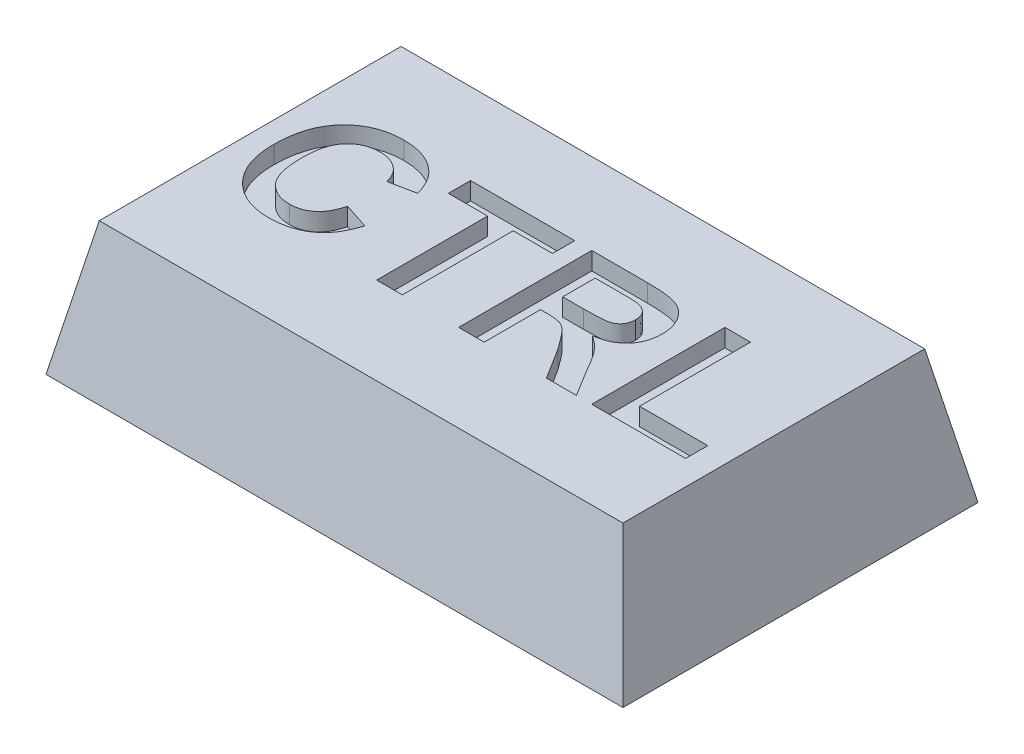
SolidWorks part; units mm, degrees
ref_plane "Front Plane" through (0, 0, 0) normal (0, 0, 1) x (1, 0, 0)
ref_plane "Top Plane" through (0, 0, 0) normal (0, 1, 0) x (1, 0, 0)
ref_plane "Right Plane" through (0, 0, 0) normal (1, 0, 0) x (0, 0, -1)
sketch "Sketch1" plane through (0, 0, 0) normal (0, 1, 0) x (1, 0, 0)
  line L1 (0, 0) -> (13, 0)
  line L2 (0, 0) -> (0, 8)
  line L3 (0, 8) -> (13, 8)
  line L4 (13, 0) -> (13, 8)
  dimension "D1" = 8
  dimension "D2" = 13
extrude "Boss-Extrude1" add sketch "Sketch1" along normal blind 3
sketch "Sketch2" plane through (0, 0, 0) normal (0, 0, 1) x (1, 0, 0)
  line L0 (0, 0) -> (0.6, 3)
  line L1 (0, 3) -> (13, 3) construction
  line L2 (0.6, 3) -> (0, 3)
  line L3 (0, 3) -> (0, 0)
  line L4 (13, 0) -> (12.4, 3)
  line L5 (12.4, 3) -> (13, 3)
  line L6 (13, 3) -> (13, 0)
  dimension "D1" = 0.6
  dimension "D2" = 0.6
extrude "Cut-Extrude1" cut sketch "Sketch2" against normal through all both and the other way through all
sketch "Sketch3" plane through (0, 0, 0) normal (1, 0, 0) x (0, 0, -1)
  line L0 (0, 0) -> (0.6, 3)
  line L1 (8, 3) -> (0, 3) construction
  line L2 (0.6, 3) -> (0, 3)
  line L3 (0, 3) -> (0, 0)
  line L4 (8, 3) -> (7.4, 3)
  line L5 (7.4, 3) -> (8, 0)
  line L6 (8, 3) -> (8, 0)
  dimension "D1" = 0.6
  dimension "D2" = 0.6
extrude "Cut-Extrude2" cut sketch "Sketch3" along normal through all both and the other way through all
sketch "Sketch4" plane through (0, 0, 0) normal (0, -1, 0) x (1, 0, 0)
  line L1 (6.5, 0) -> (6.5, -8) construction
  line L2 (13, -8) -> (0, -8) construction
  line L3 (0, 0) -> (13, 0) construction
  circle A0 centre (6.5, -3.75) radius 1.8
  dimension "D1" = 3.6
  dimension "D2" = 0
  dimension "D3" = 3.75
extrude "Cut-Extrude3" cut sketch "Sketch4" against normal blind 0.8
sketch "Sketch5" plane through (0, 0, 0) normal (0, -1, 0) x (1, 0, 0)
  line L5 (0, 0) -> (13, 0) construction
  line L6 (2.5, -8) -> (10.5, -8)
  line L7 (2.5, -8) -> (2.5, -6.9)
  line L8 (2.5, -6.9) -> (10.5, -6.9)
  line L9 (10.5, -8) -> (10.5, -6.9)
  point P2 (6.5, 0)
  dimension "D1" = 1.1
  dimension "D2" = 4
  dimension "D3" = 4
extrude "Boss-Extrude2" add sketch "Sketch5" along normal blind 2
fillet "Fillet1" radius 4 2 edges at (10.5, -2, -7.45) (2.5, -2, -7.45)
sketch "Sketch6" plane through (0, 3, 0) normal (0, 1, 0) x (1, 0, 0)
  text T0 "CTRL" font "Arial" height 3
extrude "Cut-Extrude4" cut sketch "Sketch6" against normal blind 0.4
